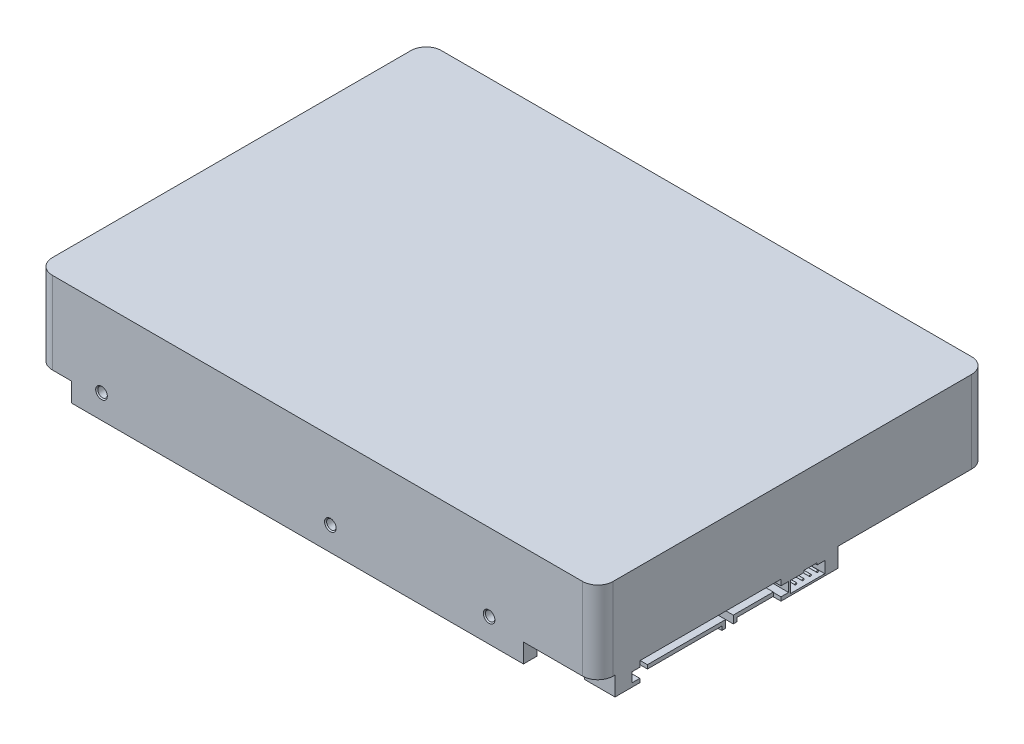
SolidWorks part; units mm, degrees
ref_plane "前视基准面" through (0, 0, 0) normal (0, 0, 1) x (1, 0, 0)
ref_plane "上视基准面" through (0, 0, 0) normal (0, 1, 0) x (1, 0, 0)
ref_plane "右视基准面" through (0, 0, 0) normal (1, 0, 0) x (0, 0, -1)
sketch "草图2" plane through (0, 0, 0) normal (0, 1, 0) x (1, 0, 0)
  line L0 (0, 182.0045) -> (0, -118854.8042) construction
  line L2 (-188.6109, 0) -> (118848.1979, 0) construction
  line L4 (0, -55) -> (0, 55) construction
  line L5 (-73.5, 51) -> (73.5, 51)
  line L6 (-73.5, 51) -> (-73.5, -51)
  line L7 (-73.5, -51) -> (73.5, -51)
  line L8 (73.5, 51) -> (73.5, -51)
  line L9 (-55, 0) -> (55, 0) construction
  dimension "D1" = 147
  dimension "D2" = 102
extrude "凸台-拉伸1" add sketch "草图2" along normal blind 26.5
sketch "草图4" plane through (0, 0, 0) normal (0, -1, 0) x (1, 0, 0)
  line L0 (45, 50.1379) -> (45, -49949.8621) construction
  line L1 (42, 47.5) -> (48, 47.5)
  line L2 (42, 47.5) -> (42, 44.5)
  line L3 (42, 44.5) -> (48, 44.5)
  line L4 (48, 47.5) -> (48, 44.5)
  line L5 (73.5, 51) -> (73.5, -51) construction
  line L6 (-73.5, 51) -> (73.5, 51) construction
  point P6 (45, 47.5)
  dimension "D1" = 28.5
  dimension "D2" = 3.5
  dimension "D3" = 6
  dimension "D4" = 3
extrude "切除-拉伸2" cut sketch "草图4" against normal blind 9
pattern_linear "阵列(线性)1" count 2 spacing 41.61 along (-1, 0, 0) count 2 spacing 101.6 along (-1, 0, 0) of "切除-拉伸2" pattern seed only yes
mirror "镜向1" about plane through (0, 0, 0) normal (0, 0, 1) of "切除-拉伸2", "阵列(线性)1"
hole_wizard "M3 螺纹孔1" positions "草图5" profile "草图6" tap size "M3" standard "GB"
sketch "草图5" plane through (0, 0, 51) normal (0, 0, 1) x (1, 0, 0)
  line L0 (73.5, 26.5) -> (73.5, 0) construction
  line L1 (-73.5, 0) -> (73.5, 0) construction
  point P0 (45, 6.25)
  point P2 (47.9025, 43.9121)
  dimension "D1" = 28.5
  dimension "D2" = 6.25
sketch "草图6" plane through (45, 6.25, 51) normal (1, 0, 0) x (0, -1, 0)
  line L0 (0, 0) -> (0, 4.7511)
  line L1 (0, 4.7511) -> (1.25, 4)
  line L2 (1.25, 4) -> (1.25, 0.275)
  line L3 (1.25, 0.275) -> (1.525, 0)
  line L5 (1.525, 0) -> (0, 0)
  line L6 (-1.25, 0.275) -> (-1.525, 0) construction
  line L10 (0, 4.7511) -> (-1.25, 4) construction
  line L11 (0, -6.35) -> (0, 107.95) construction
  dimension "螺纹孔钻头直径" = 2.5
  dimension "螺纹孔钻头深度" = 4
  dimension "近端锥形沉头孔直径" = 3.05
  dimension "近端锥形沉头孔角度" = 90
  dimension "导头角度" = 118
cosmetic thread "孔螺蚊线3" parameters "D1"=3.5, "D2"=3
pattern_linear "阵列(线性)2" count 2 spacing 41.61 along (-1, 0, 0) count 2 spacing 101.6 along (-1, 0, 0) of "M3 螺纹孔1" pattern seed only yes
mirror "镜向2" about plane through (0, 0, 0) normal (0, 0, 1) of "M3 螺纹孔1", "阵列(线性)2"
hole_wizard "M3 螺纹孔2" positions "草图8" profile "草图9" tap size "M3" standard "GB"
sketch "草图8" plane through (0, 0, 0) normal (0, -1, 0) x (-1, 0, 0)
  line L0 (-73.5, -51) -> (-73.5, 51) construction
  line L4 (-57.7616, 0) -> (49942.2384, 0) construction
  line L6 (-14.575, 0) -> (14.575, 0) construction
  point P0 (-32.22, -47.5)
  dimension "D1" = 41.28
  dimension "D2" = 47.5
sketch "草图9" plane through (32.22, 0, 47.5) normal (1, 0, 0) x (0, 0, -1)
  line L0 (0, 0) -> (0, 10.7511)
  line L1 (0, 10.7511) -> (1.25, 10)
  line L2 (1.25, 10) -> (1.25, 0.275)
  line L3 (1.25, 0.275) -> (1.525, 0)
  line L5 (1.525, 0) -> (0, 0)
  line L6 (-1.25, 0.275) -> (-1.525, 0) construction
  line L10 (0, 10.7511) -> (-1.25, 10) construction
  line L11 (0, -6.35) -> (0, 107.95) construction
  dimension "螺纹孔钻头直径" = 2.5
  dimension "螺纹孔钻头深度" = 10
  dimension "近端锥形沉头孔直径" = 3.05
  dimension "近端锥形沉头孔角度" = 90
  dimension "导头角度" = 118
cosmetic thread "孔螺蚊线2" parameters "D1"=9, "D2"=3
pattern_linear "阵列(线性)4" count 2 spacing 44.45 along (-1, 0, 0) count 2 spacing 95 along (0, 0, -1) of "M3 螺纹孔2"
sketch "草图3" plane through (0, 0, 51) normal (0, 0, 1) x (1, 0, 0)
  line L1 (-73.5, 0) -> (-64.5, 0)
  line L2 (-73.5, 0) -> (-73.5, 5)
  line L3 (-73.5, 5) -> (-64.5, 5)
  line L4 (-64.5, 0) -> (-64.5, 5)
  dimension "D1" = 9
  dimension "D2" = 5
extrude "切除-拉伸1" cut sketch "草图3" against normal through all
sketch "草图10" plane through (0, 0, 0) normal (0, -1, 0) x (1, 0, 0)
  line L0 (-64.5, -51) -> (-64.5, 51) construction
  line L1 (-64.5, 47.5) -> (-15.73, 47.5)
  line L2 (-64.5, 47.5) -> (-64.5, -47.5)
  line L3 (-64.5, -47.5) -> (-15.73, -47.5)
  line L4 (7.5, 46.5) -> (7.5, -34.5)
  line L5 (73.5, 51) -> (73.5, -51) construction
  line L6 (7.5, -34.5) -> (32.5, -34.5)
  line L8 (35.72, -47.5) -> (54, -47.5)
  line L10 (32.5, -34.5) -> (38.5, -28.5)
  line L11 (38.5, -28.5) -> (65.5, -28.5)
  line L13 (73.5, -51) -> (73.5, -12)
  line L16 (73.5, -12) -> (65.5, -12)
  line L17 (65.5, -28.5) -> (65.5, -12)
  line L18 (-71.9828, 0) -> (49928.0172, 0) construction
  line L20 (14.575, 0) -> (-14.575, 0) construction
  line L21 (-12.23, 47.5) -> (-12.23, -49952.5) construction
  line L22 (-8.73, 47.5) -> (4.2464, 47.5)
  line L23 (-8.73, -47.5) -> (28.72, -47.5)
  line L24 (7.5, 46.5) -> (27.8325, 46.5)
  line L25 (36.6075, 46.5) -> (73.5, 46.5)
  line L26 (73.5, 46.5) -> (73.5, 51)
  line L27 (73.5, 51) -> (54, 51)
  line L28 (-64.5, 51) -> (73.5, 51) construction
  line L29 (54, 51) -> (54, 47.5)
  line L30 (54, 47.5) -> (35.72, 47.5)
  line L31 (28.72, 47.5) -> (4.2464, 47.5)
  line L33 (73.5, -51) -> (54, -51)
  line L36 (54, -51) -> (54, -47.5)
  arc A0 (-15.73, 47.5) -> (-8.73, 47.5) centre (-12.23, 47.5) ccw
  arc A1 (-8.73, -47.5) -> (-15.73, -47.5) centre (-12.23, -47.5) ccw
  arc A2 (35.72, -47.5) -> (28.72, -47.5) centre (32.22, -47.5) ccw
  arc A3 (28.72, 47.5) -> (35.72, 47.5) centre (32.22, 47.5) ccw
  arc A4 (27.8325, 46.5) -> (36.6075, 46.5) centre (32.22, 47.5) ccw
  dimension "D7" = 7
  dimension "D8" = 7
  dimension "D9" = 7
  dimension "D10" = 7
  dimension "D11" = 9
  dimension "D1" = 95
  dimension "D2" = 13
  dimension "D3" = 135
  dimension "D4" = 25
  dimension "D5" = 66
  dimension "D6" = 27
  dimension "D12" = 81
  dimension "D13" = 75
  dimension "D14" = 16.5
  dimension "D15" = 19.5
extrude "切除-拉伸8" cut sketch "草图10" against normal blind 5
sketch "草图11" plane through (0, 0, 0) normal (0, -1, 0) x (1, 0, 0)
  line L0 (48, 46.5) -> (73.5, 46.5) construction
  line L1 (65.5, 46.5) -> (36.6075, 46.5)
  line L2 (65.5, 46.5) -> (65.5, 42.5)
  line L3 (65.5, -34.5) -> (7.5, -34.5)
  line L4 (7.5, 46.5) -> (7.5, -34.5)
  line L6 (65.5, 42.5) -> (61.5, 42.5)
  line L8 (65.5, 38.5) -> (61.5, 38.5)
  line L9 (61.5, 42.5) -> (61.5, 38.5)
  line L14 (65.5, 3) -> (61.5, 3)
  line L16 (65.5, -0.5) -> (61.5, -0.5)
  line L17 (61.5, 3) -> (61.5, -0.5)
  line L22 (65.5, -12) -> (65.5, -28.5) construction
  line L23 (65.5, 38.5) -> (65.5, 17.5)
  line L24 (65.5, -12) -> (61.5, -12)
  line L26 (65.5, -9.5) -> (61.5, -9.5)
  line L27 (61.5, -12) -> (61.5, -9.5)
  line L28 (65.5, -0.5) -> (65.5, -9.5)
  line L29 (65.5, -12) -> (65.5, -34.5)
  line L30 (27.8325, 46.5) -> (7.5, 46.5)
  line L32 (65.5, 17.5) -> (64, 17.5)
  line L34 (65.5, 15.5) -> (64, 15.5)
  line L35 (64, 17.5) -> (64, 15.5)
  line L47 (65.5, 15.5) -> (65.5, 3)
  arc A0 (27.8325, 46.5) -> (36.6075, 46.5) centre (32.22, 47.5) ccw
  dimension "D1" = 2.5
  dimension "D10" = 4.5
  dimension "D2" = 3.5
  dimension "D3" = 15
  dimension "D4" = 4
  dimension "D5" = 4
  dimension "D6" = 1.5
  dimension "D7" = 2
  dimension "D8" = 4
  dimension "D9" = 21
extrude "切除-拉伸9" cut sketch "草图11" against normal blind 0.5
sketch "草图12" plane through (0, 0, 0) normal (0, -1, 0) x (1, 0, 0)
  line L0 (73.5, 46.5) -> (73.5, -12) construction
  line L1 (68.5, 40) -> (73.5, 40)
  line L2 (68.5, 40) -> (68.5, 3)
  line L3 (68.5, 3) -> (73.5, 3)
  line L4 (73.5, 40) -> (73.5, 3)
  line L5 (48, 46.5) -> (73.5, 46.5) construction
  dimension "D1" = 37
  dimension "D2" = 6.5
  dimension "D3" = 5
extrude "切除-拉伸10" cut sketch "草图12" against normal blind 5
sketch "草图13" plane through (73.5, 0, 0) normal (1, 0, 0) x (0, 0, -1)
  line L0 (56.1, 0) -> (-56.1, 0) construction
  line L1 (-42, 3.5) -> (-39, 3.5)
  line L2 (-42, 3.5) -> (-42, 1)
  line L3 (-42, 1) -> (-39, 1)
  line L4 (-39, 3.5) -> (-39, 1)
  line L5 (-4, 3.5) -> (-1, 3.5)
  line L6 (-4, 3.5) -> (-4, 1)
  line L7 (-4, 1) -> (-1, 1)
  line L8 (-1, 3.5) -> (-1, 1)
  line L9 (-40, 5) -> (-40, 0) construction
  dimension "D1" = 2.5
  dimension "D2" = 41
  dimension "D3" = 1
  dimension "D4" = 3
  dimension "D5" = 2
extrude "切除-拉伸11" cut sketch "草图13" against normal blind 8
sketch "草图14" plane through (68.5, 0, 0) normal (1, 0, 0) x (0, 0, -1)
  line L0 (-15.5, 3.1) -> (-5, 3.1)
  line L1 (-38, 3.1) -> (-17.5, 3.1)
  line L2 (-38, 3.1) -> (-38, 2.1)
  line L3 (-38, 2.1) -> (-18.5, 2.1)
  line L6 (-18.5, 2.1) -> (-18.5, 1.1)
  line L7 (-18.5, 1.1) -> (-17.5, 1.1)
  line L8 (-17.5, 3.1) -> (-17.5, 1.1)
  line L10 (-15.5, 3.1) -> (-15.5, 1.1)
  line L11 (-15.5, 1.1) -> (-14.5, 1.1)
  line L12 (-14.5, 2.1) -> (-14.5, 1.1)
  line L15 (-14.5, 2.1) -> (-5, 2.1)
  line L16 (-5, 3.1) -> (-5, 2.1)
  line L17 (-40, 1) -> (-40, 0) construction
  line L18 (56.1, 0) -> (-56.1, 0) construction
  dimension "D1" = 1
  dimension "D2" = 2
  dimension "D3" = 19.5
  dimension "D4" = 9.5
  dimension "D5" = 2
  dimension "D6" = 1.1
  dimension "D7" = 1
extrude "凸台-拉伸2" add sketch "草图14" along normal up to surface (5 mm away) up to face at (73.5, 5.05, 16.35)
sketch "草图15" plane through (73.5, 0, 0) normal (1, 0, 0) x (0, 0, -1)
  line L0 (6.5, 3.5) -> (8.5, 3.5)
  line L1 (-0.5, 3.5) -> (3, 3.5)
  line L2 (-0.5, 3.5) -> (-0.5, 0.5)
  line L3 (-0.5, 0.5) -> (8.5, 0.5)
  line L4 (8.5, 3.5) -> (8.5, 0.5)
  line L6 (3, 3.5) -> (3, 4)
  line L7 (3, 4) -> (6.5, 4)
  line L8 (6.5, 3.5) -> (6.5, 4)
  line L9 (-1, 1) -> (-1, 3.5) construction
  line L11 (28.5, 0.5) -> (12, 0.5) construction
  line L12 (56.1, 0) -> (-56.1, 0) construction
  point P10 (-1, 2.25)
  dimension "D1" = 0.5
  dimension "D2" = 3.5
  dimension "D3" = 9
  dimension "D4" = 0.5
  dimension "D5" = 3
  dimension "D6" = 2
  dimension "D7" = 0.5
extrude "切除-拉伸12" cut sketch "草图15" against normal blind 5
sketch "草图16" plane through (0, 2.1, 0) normal (0, -1, 0) x (1, 0, 0)
  line L0 (68.5, 40) -> (68.5, 3) construction
  line L1 (68.5, 37.9) -> (73, 37.9)
  line L2 (68.5, 37.9) -> (68.5, 36.9)
  line L3 (68.5, 36.9) -> (73, 36.9)
  line L6 (73, 37.9) -> (73, 36.9)
  line L7 (73.5, 38) -> (68.5, 38) construction
  dimension "D1" = 4.5
  dimension "D2" = 1
  dimension "D3" = 0.1
extrude "凸台-拉伸3" add sketch "草图16" along normal blind 0.1
pattern_linear "阵列(线性)5" count 15 spacing 1.3 along (0, 0, -1) of "凸台-拉伸3"
sketch "草图17" plane through (0, 2.1, 0) normal (0, -1, 0) x (1, 0, 0)
  line L0 (68.5, 14.5) -> (68.5, 5) construction
  line L1 (68.5, 6.4) -> (73, 6.4)
  line L2 (68.5, 6.4) -> (68.5, 5.4)
  line L3 (68.5, 5.4) -> (73, 5.4)
  line L4 (73, 6.4) -> (73, 5.4)
  line L5 (73.5, 5) -> (68.5, 5) construction
  dimension "D1" = 4.5
  dimension "D2" = 0.4
  dimension "D3" = 1
extrude "凸台-拉伸4" add sketch "草图17" along normal blind 0.1
pattern_linear "阵列(线性)6" count 7 spacing 1.3 along (0, 0, 1) of "凸台-拉伸4"
sketch "草图18" plane through (68.5, 0, 0) normal (1, 0, 0) x (0, 0, -1)
  line L0 (-0.5, 2) -> (49999.5, 2) construction
  line L1 (-0.5, 3.5) -> (-0.5, 0.5) construction
  line L2 (8.5, 0.5) -> (8.5, 3.5) construction
  circle A0 centre (0.9, 2) radius 0.25
  point P4 (-0.5, 2)
  point P7 (8.5, 2)
  dimension "D1" = 0.5
  dimension "D2" = 1.4
extrude "凸台-拉伸5" add sketch "草图18" along normal up to surface (5 mm away) up to face at (73.5, 2.875, -4.375)
pattern_linear "阵列(线性)7" count 4 spacing 1.9 along (0, 0, -1) of "凸台-拉伸5"
fillet "圆角1" radius 4 4 edges at (73.5, 15.75, 51) (73.5, 15.75, -51) (-73.5, 15.75, -51) (-73.5, 15.75, 51)
chamfer "倒角1" distance 0.1 angle 45 22 edges at (73, 2, 19.2) (73, 2, 20.5) (73, 2, 21.8) (73, 2, 23.1) (73, 2, 24.4) (73, 2, 25.7) (73, 2, 27) (73, 2, 28.3) (73, 2, 29.6) (73, 2, 30.9) (73, 2, 32.2) (73, 2, 33.5) (73, 2, 34.8) (73, 2, 36.1) (73, 2, 37.4) (73, 2, 13.7) (73, 2, 12.4) (73, 2, 11.1) (73, 2, 9.8) (73, 2, 8.5) (73, 2, 7.2) (73, 2, 5.9)
